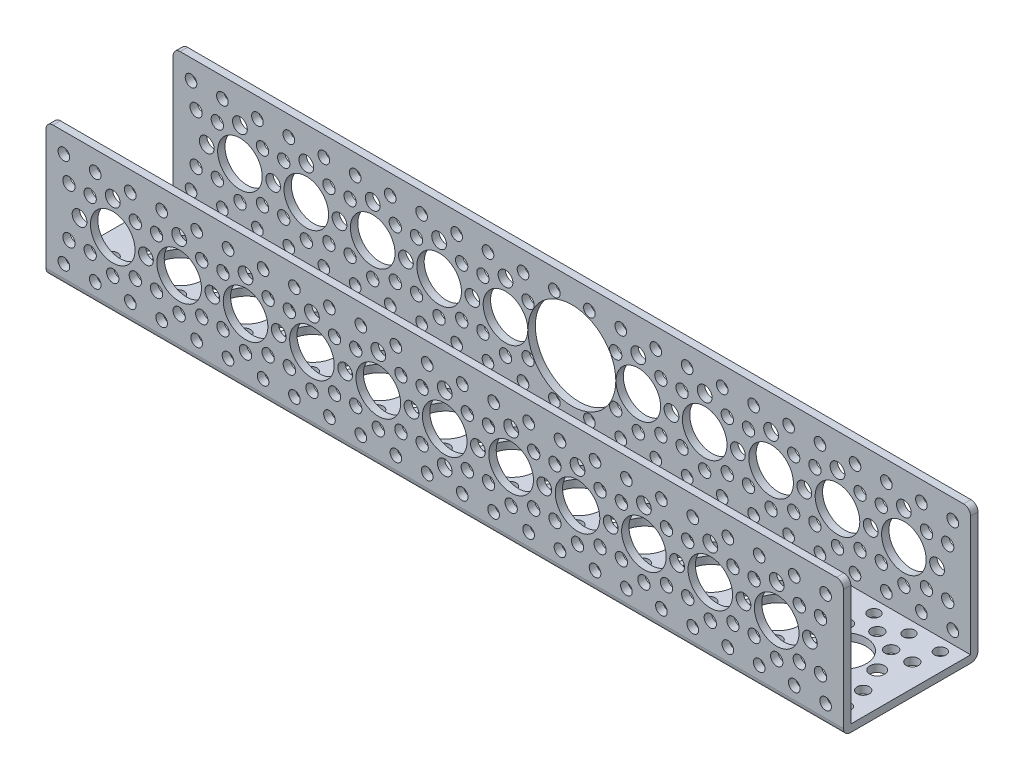
SolidWorks part; units mm, degrees
material "1060 合金"
ref_plane "前视基准面" through (0, 0, 0) normal (0, 0, 1) x (1, 0, 0)
ref_plane "上视基准面" through (0, 0, 0) normal (0, 1, 0) x (1, 0, 0)
ref_plane "右视基准面" through (0, 0, 0) normal (1, 0, 0) x (0, 0, -1)
other "Configuration Table"
sketch "草图1" plane through (0, 0, 0) normal (0, 1, 0) x (1, 0, 0)
  line L1 (-113.5, 19.15) -> (113.5, 19.15)
  line L2 (-113.5, 19.15) -> (-113.5, -19.15)
  line L3 (-113.5, -19.15) -> (113.5, -19.15)
  line L4 (113.5, 19.15) -> (113.5, -19.15)
  line L5 (-113.5, 19.15) -> (113.5, -19.15) construction
  line L6 (-113.5, -19.15) -> (113.5, 19.15) construction
  point P0 (0, 0)
  dimension "D1" = 227
  dimension "D2" = 38.3
extrude "凸台-拉伸1" add sketch "草图1" along normal blind 38.3
shell "抽壳1" thickness 2.1 removed face at (-113.5, 19.15, 0) removed face at (113.5, 19.15, 0) removed face at (0, 38.3, 0)
fillet "圆角1" radius 2 6 edges at (113.5, 38.3, 18.1) (113.5, 38.3, -18.1) (-113.5, 38.3, -18.1) (-113.5, 38.3, 18.1) (0, 0, -19.15) (0, 0, 19.15)
sketch "草图2" plane through (0, 0, 0) normal (0, -1, 0) x (1, 0, 0)
  line L0 (0, 0) -> (0, 50000) construction
  line L1 (0, 0) -> (50000, 0) construction
  line L2 (0, 9.5) -> (4.986, 13.5194) construction
  line L3 (0, 9.5) -> (6.4289, 6.9942) construction
  line L4 (4.986, 13.5194) -> (6.4289, 6.9942) construction
  line L5 (0, 0) -> (6.4289, 6.9942) construction
  line L6 (103.95, 0) -> (103.95, 50000) construction
  line L7 (-4.986, 13.5194) -> (-6.4289, 6.9942) construction
  circle A0 centre (0, 0) radius 6.35
  circle A1 centre (18.9, 0) radius 6.35
  circle A2 centre (37.8, 0) radius 6.35
  circle A3 centre (56.7, 0) radius 6.35
  circle A4 centre (75.6, 0) radius 6.35
  circle A5 centre (94.5, 0) radius 6.35
  circle A6 centre (-94.5, 0) radius 6.35
  circle A7 centre (-75.6, 0) radius 6.35
  circle A8 centre (-56.7, 0) radius 6.35
  circle A9 centre (-37.8, 0) radius 6.35
  circle A10 centre (-18.9, 0) radius 6.35
  circle A11 centre (0, 9.5) radius 1.75
  circle A12 centre (9.45, 0) radius 2.1
  circle A13 centre (4.986, 13.5194) radius 1.6544
  circle A14 centre (6.4289, 6.9942) radius 1.75
  circle A15 centre (-9.45, 0) radius 2.1
  circle A16 centre (-6.4289, 6.9942) radius 1.75
  circle A17 centre (-4.986, 13.5194) radius 1.6544
  circle A18 centre (6.4289, -6.9942) radius 1.75
  circle A19 centre (4.986, -13.5194) radius 1.6544
  circle A20 centre (0, -9.5) radius 1.75
  circle A21 centre (-4.986, -13.5194) radius 1.6544
  circle A22 centre (-6.4289, -6.9942) radius 1.75
  circle A23 centre (9.45, 0) radius 2.1
  circle A24 centre (12.4711, 6.9942) radius 1.75
  circle A25 centre (13.914, 13.5194) radius 1.6544
  circle A26 centre (12.4711, -6.9942) radius 1.75
  circle A27 centre (13.914, -13.5194) radius 1.6544
  circle A28 centre (18.9, -9.5) radius 1.75
  circle A29 centre (23.886, -13.5194) radius 1.6544
  circle A30 centre (25.3289, -6.9942) radius 1.75
  circle A31 centre (28.35, 0) radius 2.1
  circle A32 centre (25.3289, 6.9942) radius 1.75
  circle A33 centre (18.9, 9.5) radius 1.75
  circle A34 centre (23.886, 13.5194) radius 1.6544
  circle A35 centre (28.35, 0) radius 2.1
  circle A36 centre (31.3711, 6.9942) radius 1.75
  circle A37 centre (32.814, 13.5194) radius 1.6544
  circle A38 centre (31.3711, -6.9942) radius 1.75
  circle A39 centre (32.814, -13.5194) radius 1.6544
  circle A40 centre (37.8, -9.5) radius 1.75
  circle A41 centre (42.786, -13.5194) radius 1.6544
  circle A42 centre (44.2289, -6.9942) radius 1.75
  circle A43 centre (47.25, 0) radius 2.1
  circle A44 centre (44.2289, 6.9942) radius 1.75
  circle A45 centre (37.8, 9.5) radius 1.75
  circle A46 centre (42.786, 13.5194) radius 1.6544
  circle A47 centre (47.25, 0) radius 2.1
  circle A48 centre (50.2711, 6.9942) radius 1.75
  circle A49 centre (51.714, 13.5194) radius 1.6544
  circle A50 centre (50.2711, -6.9942) radius 1.75
  circle A51 centre (51.714, -13.5194) radius 1.6544
  circle A52 centre (56.7, -9.5) radius 1.75
  circle A53 centre (61.686, -13.5194) radius 1.6544
  circle A54 centre (63.1289, -6.9942) radius 1.75
  circle A55 centre (66.15, 0) radius 2.1
  circle A56 centre (63.1289, 6.9942) radius 1.75
  circle A57 centre (56.7, 9.5) radius 1.75
  circle A58 centre (61.686, 13.5194) radius 1.6544
  circle A59 centre (66.15, 0) radius 2.1
  circle A60 centre (69.1711, 6.9942) radius 1.75
  circle A61 centre (70.614, 13.5194) radius 1.6544
  circle A62 centre (69.1711, -6.9942) radius 1.75
  circle A63 centre (70.614, -13.5194) radius 1.6544
  circle A64 centre (75.6, -9.5) radius 1.75
  circle A65 centre (80.586, -13.5194) radius 1.6544
  circle A66 centre (82.0289, -6.9942) radius 1.75
  circle A67 centre (85.05, 0) radius 2.1
  circle A68 centre (82.0289, 6.9942) radius 1.75
  circle A69 centre (75.6, 9.5) radius 1.75
  circle A70 centre (80.586, 13.5194) radius 1.6544
  circle A71 centre (85.05, 0) radius 2.1
  circle A72 centre (88.0711, 6.9942) radius 1.75
  circle A73 centre (89.514, 13.5194) radius 1.6544
  circle A74 centre (88.0711, -6.9942) radius 1.75
  circle A75 centre (89.514, -13.5194) radius 1.6544
  circle A76 centre (94.5, -9.5) radius 1.75
  circle A77 centre (99.486, -13.5194) radius 1.6544
  circle A78 centre (100.9289, -6.9942) radius 1.75
  circle A79 centre (103.95, 0) radius 2.1
  circle A80 centre (100.9289, 6.9942) radius 1.75
  circle A81 centre (94.5, 9.5) radius 1.75
  circle A82 centre (99.486, 13.5194) radius 1.6544
  circle A83 centre (108.414, -13.5194) radius 1.6544
  circle A84 centre (106.9711, -6.9942) radius 1.75
  circle A85 centre (106.9711, 6.9942) radius 1.75
  circle A86 centre (108.414, 13.5194) radius 1.6544
  circle A87 centre (-108.414, 13.5194) radius 1.6544
  circle A88 centre (-106.9711, 6.9942) radius 1.75
  circle A89 centre (-106.9711, -6.9942) radius 1.75
  circle A90 centre (-108.414, -13.5194) radius 1.6544
  circle A91 centre (-99.486, 13.5194) radius 1.6544
  circle A92 centre (-94.5, 9.5) radius 1.75
  circle A93 centre (-100.9289, 6.9942) radius 1.75
  circle A94 centre (-103.95, 0) radius 2.1
  circle A95 centre (-100.9289, -6.9942) radius 1.75
  circle A96 centre (-99.486, -13.5194) radius 1.6544
  circle A97 centre (-94.5, -9.5) radius 1.75
  circle A98 centre (-89.514, -13.5194) radius 1.6544
  circle A99 centre (-88.0711, -6.9942) radius 1.75
  circle A100 centre (-89.514, 13.5194) radius 1.6544
  circle A101 centre (-88.0711, 6.9942) radius 1.75
  circle A102 centre (-85.05, 0) radius 2.1
  circle A103 centre (-80.586, 13.5194) radius 1.6544
  circle A104 centre (-75.6, 9.5) radius 1.75
  circle A105 centre (-82.0289, 6.9942) radius 1.75
  circle A106 centre (-85.05, 0) radius 2.1
  circle A107 centre (-82.0289, -6.9942) radius 1.75
  circle A108 centre (-80.586, -13.5194) radius 1.6544
  circle A109 centre (-75.6, -9.5) radius 1.75
  circle A110 centre (-70.614, -13.5194) radius 1.6544
  circle A111 centre (-69.1711, -6.9942) radius 1.75
  circle A112 centre (-70.614, 13.5194) radius 1.6544
  circle A113 centre (-69.1711, 6.9942) radius 1.75
  circle A114 centre (-66.15, 0) radius 2.1
  circle A115 centre (-61.686, 13.5194) radius 1.6544
  circle A116 centre (-56.7, 9.5) radius 1.75
  circle A117 centre (-63.1289, 6.9942) radius 1.75
  circle A118 centre (-66.15, 0) radius 2.1
  circle A119 centre (-63.1289, -6.9942) radius 1.75
  circle A120 centre (-61.686, -13.5194) radius 1.6544
  circle A121 centre (-56.7, -9.5) radius 1.75
  circle A122 centre (-51.714, -13.5194) radius 1.6544
  circle A123 centre (-50.2711, -6.9942) radius 1.75
  circle A124 centre (-51.714, 13.5194) radius 1.6544
  circle A125 centre (-50.2711, 6.9942) radius 1.75
  circle A126 centre (-47.25, 0) radius 2.1
  circle A127 centre (-42.786, 13.5194) radius 1.6544
  circle A128 centre (-37.8, 9.5) radius 1.75
  circle A129 centre (-44.2289, 6.9942) radius 1.75
  circle A130 centre (-47.25, 0) radius 2.1
  circle A131 centre (-44.2289, -6.9942) radius 1.75
  circle A132 centre (-42.786, -13.5194) radius 1.6544
  circle A133 centre (-37.8, -9.5) radius 1.75
  circle A134 centre (-32.814, -13.5194) radius 1.6544
  circle A135 centre (-31.3711, -6.9942) radius 1.75
  circle A136 centre (-32.814, 13.5194) radius 1.6544
  circle A137 centre (-31.3711, 6.9942) radius 1.75
  circle A138 centre (-28.35, 0) radius 2.1
  circle A139 centre (-23.886, 13.5194) radius 1.6544
  circle A140 centre (-18.9, 9.5) radius 1.75
  circle A141 centre (-25.3289, 6.9942) radius 1.75
  circle A142 centre (-28.35, 0) radius 2.1
  circle A143 centre (-25.3289, -6.9942) radius 1.75
  circle A144 centre (-23.886, -13.5194) radius 1.6544
  circle A145 centre (-18.9, -9.5) radius 1.75
  circle A146 centre (-13.914, -13.5194) radius 1.6544
  circle A147 centre (-12.4711, -6.9942) radius 1.75
  circle A148 centre (-13.914, 13.5194) radius 1.6544
  circle A149 centre (-12.4711, 6.9942) radius 1.75
  circle A150 centre (-9.45, 0) radius 2.1
  circle A151 centre (-9.45, 0) radius 2.1
  circle A152 centre (-94.5, 0) radius 6.35
  circle A153 centre (-75.6, 0) radius 6.35
  circle A154 centre (-56.7, 0) radius 6.35
  circle A155 centre (-37.8, 0) radius 6.35
  circle A156 centre (-18.9, 0) radius 6.35
  point P27 (0, 7.75)
  point P28 (0, 6.35)
  point P31 (6.35, 0)
  point P32 (7.35, 0)
  point P35 (4.986, 15.1737)
  point P38 (1.3624, 10.5983)
  point P39 (3.6981, 12.4811)
  point P42 (5.3432, 11.904)
  point P43 (6.0511, 8.7029)
  point P44 (1.6305, 8.8645)
  point P45 (4.7984, 7.6297)
  point P46 (4.2972, 4.6751)
  point P47 (5.2446, 5.7058)
  point P323 (-5.2446, 5.7058)
  point P324 (-4.7984, 7.6297)
  point P325 (-6.0511, 8.7029)
  point P326 (-5.3432, 11.904)
  point P327 (-4.986, 15.1737)
  point P328 (-7.35, 0)
  point P329 (-6.35, 0)
  dimension "D1" = 12.7
  dimension "D3" = 3.5
  dimension "D5" = 4.2
  dimension "D7" = 3.3087
  dimension "D10" = 3.5
  dimension "D4" = 1.4
  dimension "D6" = 1
  dimension "D8" = 1.4
  dimension "D9" = 3
  dimension "D11" = 3.2784
  dimension "D12" = 3.4
  dimension "D13" = 6
  dimension "D2" = 6
extrude "切除-拉伸1" cut sketch "草图2" against normal up to next (2.1 mm away)
sketch "草图4" plane through (0, 0, 19.15) normal (0, 0, 1) x (1, 0, 0)
  line L0 (0, 0) -> (0, 38.3) construction
  line L1 (-111.5, 38.3) -> (111.5, 38.3) construction
  line L2 (0, 19.15) -> (0, 50019.15) construction
  line L3 (0, 19.15) -> (50000, 19.15) construction
  line L4 (0, 28.65) -> (4.986, 32.6694) construction
  line L5 (0, 28.65) -> (6.4289, 26.1442) construction
  line L6 (4.986, 32.6694) -> (6.4289, 26.1442) construction
  line L7 (0, 19.15) -> (6.4289, 26.1442) construction
  line L8 (103.95, 19.15) -> (103.95, 50019.15) construction
  line L9 (-4.986, 32.6694) -> (-6.4289, 26.1442) construction
  circle A0 centre (0, 19.15) radius 6.35
  circle A1 centre (18.9, 19.15) radius 6.35
  circle A2 centre (37.8, 19.15) radius 6.35
  circle A3 centre (56.7, 19.15) radius 6.35
  circle A4 centre (75.6, 19.15) radius 6.35
  circle A5 centre (94.5, 19.15) radius 6.35
  circle A6 centre (-94.5, 19.15) radius 6.35
  circle A7 centre (-75.6, 19.15) radius 6.35
  circle A8 centre (-56.7, 19.15) radius 6.35
  circle A9 centre (-37.8, 19.15) radius 6.35
  circle A10 centre (-18.9, 19.15) radius 6.35
  circle A11 centre (0, 28.65) radius 2.1
  circle A12 centre (9.45, 19.15) radius 2.1
  circle A13 centre (4.986, 32.6694) radius 1.6544
  circle A14 centre (6.4289, 26.1442) radius 1.75
  circle A15 centre (-9.45, 19.15) radius 2.1
  circle A16 centre (-6.4289, 26.1442) radius 1.75
  circle A17 centre (-4.986, 32.6694) radius 1.6544
  circle A18 centre (6.4289, 12.1558) radius 1.75
  circle A19 centre (4.986, 5.6306) radius 1.6544
  circle A20 centre (0, 9.65) radius 2.1
  circle A21 centre (-4.986, 5.6306) radius 1.6544
  circle A22 centre (-6.4289, 12.1558) radius 1.75
  circle A23 centre (9.45, 19.15) radius 2.1
  circle A24 centre (12.4711, 26.1442) radius 1.75
  circle A25 centre (13.914, 32.6694) radius 1.6544
  circle A26 centre (12.4711, 12.1558) radius 1.75
  circle A27 centre (13.914, 5.6306) radius 1.6544
  circle A28 centre (18.9, 9.65) radius 1.75
  circle A29 centre (23.886, 5.6306) radius 1.6544
  circle A30 centre (25.3289, 12.1558) radius 1.75
  circle A31 centre (28.35, 19.15) radius 2.1
  circle A32 centre (25.3289, 26.1442) radius 1.75
  circle A33 centre (18.9, 28.65) radius 2.1
  circle A34 centre (23.886, 32.6694) radius 1.6544
  circle A35 centre (28.35, 19.15) radius 2.1
  circle A36 centre (31.3711, 26.1442) radius 1.75
  circle A37 centre (32.814, 32.6694) radius 1.6544
  circle A38 centre (31.3711, 12.1558) radius 1.75
  circle A39 centre (32.814, 5.6306) radius 1.6544
  circle A40 centre (37.8, 9.65) radius 1.75
  circle A41 centre (42.786, 5.6306) radius 1.6544
  circle A42 centre (44.2289, 12.1558) radius 1.75
  circle A43 centre (47.25, 19.15) radius 2.1
  circle A44 centre (44.2289, 26.1442) radius 1.75
  circle A45 centre (37.8, 28.65) radius 2.1
  circle A46 centre (42.786, 32.6694) radius 1.6544
  circle A47 centre (47.25, 19.15) radius 2.1
  circle A48 centre (50.2711, 26.1442) radius 1.75
  circle A49 centre (51.714, 32.6694) radius 1.6544
  circle A50 centre (50.2711, 12.1558) radius 1.75
  circle A51 centre (51.714, 5.6306) radius 1.6544
  circle A52 centre (56.7, 9.65) radius 1.75
  circle A53 centre (61.686, 5.6306) radius 1.6544
  circle A54 centre (63.1289, 12.1558) radius 1.75
  circle A55 centre (66.15, 19.15) radius 2.1
  circle A56 centre (63.1289, 26.1442) radius 1.75
  circle A57 centre (56.7, 28.65) radius 2.1
  circle A58 centre (61.686, 32.6694) radius 1.6544
  circle A59 centre (66.15, 19.15) radius 2.1
  circle A60 centre (69.1711, 26.1442) radius 1.75
  circle A61 centre (70.614, 32.6694) radius 1.6544
  circle A62 centre (69.1711, 12.1558) radius 1.75
  circle A63 centre (70.614, 5.6306) radius 1.6544
  circle A64 centre (75.6, 9.65) radius 1.75
  circle A65 centre (80.586, 5.6306) radius 1.6544
  circle A66 centre (82.0289, 12.1558) radius 1.75
  circle A67 centre (85.05, 19.15) radius 2.1
  circle A68 centre (82.0289, 26.1442) radius 1.75
  circle A69 centre (75.6, 28.65) radius 2.1
  circle A70 centre (80.586, 32.6694) radius 1.6544
  circle A71 centre (85.05, 19.15) radius 2.1
  circle A72 centre (88.0711, 26.1442) radius 1.75
  circle A73 centre (89.514, 32.6694) radius 1.6544
  circle A74 centre (88.0711, 12.1558) radius 1.75
  circle A75 centre (89.514, 5.6306) radius 1.6544
  circle A76 centre (94.5, 9.65) radius 1.75
  circle A77 centre (99.486, 5.6306) radius 1.6544
  circle A78 centre (100.9289, 12.1558) radius 1.75
  circle A79 centre (103.95, 19.15) radius 2.1
  circle A80 centre (100.9289, 26.1442) radius 1.75
  circle A81 centre (94.5, 28.65) radius 2.1
  circle A82 centre (99.486, 32.6694) radius 1.6544
  circle A83 centre (108.414, 5.6306) radius 1.6544
  circle A84 centre (106.9711, 12.1558) radius 1.75
  circle A85 centre (106.9711, 26.1442) radius 1.75
  circle A86 centre (108.414, 32.6694) radius 1.6544
  circle A87 centre (-108.414, 32.6694) radius 1.6544
  circle A88 centre (-106.9711, 26.1442) radius 1.75
  circle A89 centre (-106.9711, 12.1558) radius 1.75
  circle A90 centre (-108.414, 5.6306) radius 1.6544
  circle A91 centre (-99.486, 32.6694) radius 1.6544
  circle A92 centre (-94.5, 28.65) radius 2.1
  circle A93 centre (-100.9289, 26.1442) radius 1.75
  circle A94 centre (-103.95, 19.15) radius 2.1
  circle A95 centre (-100.9289, 12.1558) radius 1.75
  circle A96 centre (-99.486, 5.6306) radius 1.6544
  circle A97 centre (-94.5, 9.65) radius 1.75
  circle A98 centre (-89.514, 5.6306) radius 1.6544
  circle A99 centre (-88.0711, 12.1558) radius 1.75
  circle A100 centre (-89.514, 32.6694) radius 1.6544
  circle A101 centre (-88.0711, 26.1442) radius 1.75
  circle A102 centre (-85.05, 19.15) radius 2.1
  circle A103 centre (-80.586, 32.6694) radius 1.6544
  circle A104 centre (-75.6, 28.65) radius 2.1
  circle A105 centre (-82.0289, 26.1442) radius 1.75
  circle A106 centre (-85.05, 19.15) radius 2.1
  circle A107 centre (-82.0289, 12.1558) radius 1.75
  circle A108 centre (-80.586, 5.6306) radius 1.6544
  circle A109 centre (-75.6, 9.65) radius 1.75
  circle A110 centre (-70.614, 5.6306) radius 1.6544
  circle A111 centre (-69.1711, 12.1558) radius 1.75
  circle A112 centre (-70.614, 32.6694) radius 1.6544
  circle A113 centre (-69.1711, 26.1442) radius 1.75
  circle A114 centre (-66.15, 19.15) radius 2.1
  circle A115 centre (-61.686, 32.6694) radius 1.6544
  circle A116 centre (-56.7, 28.65) radius 2.1
  circle A117 centre (-63.1289, 26.1442) radius 1.75
  circle A118 centre (-66.15, 19.15) radius 2.1
  circle A119 centre (-63.1289, 12.1558) radius 1.75
  circle A120 centre (-61.686, 5.6306) radius 1.6544
  circle A121 centre (-56.7, 9.65) radius 1.75
  circle A122 centre (-51.714, 5.6306) radius 1.6544
  circle A123 centre (-50.2711, 12.1558) radius 1.75
  circle A124 centre (-51.714, 32.6694) radius 1.6544
  circle A125 centre (-50.2711, 26.1442) radius 1.75
  circle A126 centre (-47.25, 19.15) radius 2.1
  circle A127 centre (-42.786, 32.6694) radius 1.6544
  circle A128 centre (-37.8, 28.65) radius 2.1
  circle A129 centre (-44.2289, 26.1442) radius 1.75
  circle A130 centre (-47.25, 19.15) radius 2.1
  circle A131 centre (-44.2289, 12.1558) radius 1.75
  circle A132 centre (-42.786, 5.6306) radius 1.6544
  circle A133 centre (-37.8, 9.65) radius 1.75
  circle A134 centre (-32.814, 5.6306) radius 1.6544
  circle A135 centre (-31.3711, 12.1558) radius 1.75
  circle A136 centre (-32.814, 32.6694) radius 1.6544
  circle A137 centre (-31.3711, 26.1442) radius 1.75
  circle A138 centre (-28.35, 19.15) radius 2.1
  circle A139 centre (-23.886, 32.6694) radius 1.6544
  circle A140 centre (-18.9, 28.65) radius 2.1
  circle A141 centre (-25.3289, 26.1442) radius 1.75
  circle A142 centre (-28.35, 19.15) radius 2.1
  circle A143 centre (-25.3289, 12.1558) radius 1.75
  circle A144 centre (-23.886, 5.6306) radius 1.6544
  circle A145 centre (-18.9, 9.65) radius 1.75
  circle A146 centre (-13.914, 5.6306) radius 1.6544
  circle A147 centre (-12.4711, 12.1558) radius 1.75
  circle A148 centre (-13.914, 32.6694) radius 1.6544
  circle A149 centre (-12.4711, 26.1442) radius 1.75
  circle A150 centre (-9.45, 19.15) radius 2.1
  circle A151 centre (-9.45, 19.15) radius 2.1
  circle A152 centre (-94.5, 19.15) radius 6.35
  circle A153 centre (-75.6, 19.15) radius 6.35
  circle A154 centre (-56.7, 19.15) radius 6.35
  circle A155 centre (-37.8, 19.15) radius 6.35
  circle A156 centre (-18.9, 19.15) radius 6.35
  point P5 (0, 19.15)
  point P32 (0, 26.55)
  point P33 (0, 25.5)
  point P36 (6.35, 19.15)
  point P37 (7.35, 19.15)
  point P40 (4.986, 34.3237)
  point P43 (1.6349, 29.968)
  point P44 (3.6981, 31.6311)
  point P47 (5.3432, 31.054)
  point P48 (6.0511, 27.8529)
  point P49 (1.9566, 27.8874)
  point P50 (4.7984, 26.7797)
  point P51 (4.2972, 23.8251)
  point P52 (5.2446, 24.8558)
  point P328 (-5.2446, 24.8558)
  point P329 (-4.7984, 26.7797)
  point P330 (-6.0511, 27.8529)
  point P331 (-5.3432, 31.054)
  point P332 (-4.986, 34.3237)
  point P333 (-7.35, 19.15)
  point P334 (-6.35, 19.15)
  dimension "D1" = 4.2
extrude "切除-拉伸3" cut sketch "草图4" against normal up to surface (38.3 mm away) up to face at (0, 25.6714, -19.15)
sketch "草图5" plane through (0, 0, -19.15) normal (0, 0, -1) x (-1, 0, 0)
  circle A0 centre (0, 19.15) radius 12.5
  dimension "D1" = 25
extrude "切除-拉伸4" cut sketch "草图5" against normal up to next
